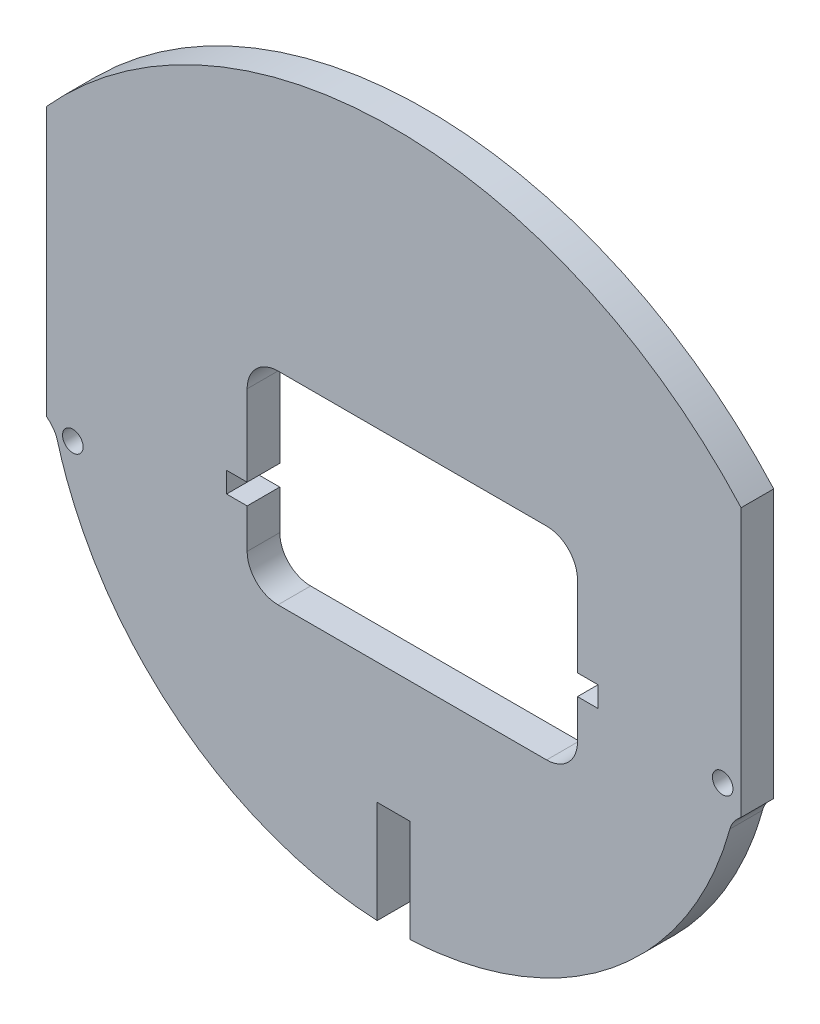
SolidWorks part; units mm, degrees
ref_plane "Front Plane" through (0, 0, 0) normal (0, 0, 1) x (1, 0, 0)
ref_plane "Top Plane" through (0, 0, 0) normal (0, 1, 0) x (1, 0, 0)
ref_plane "Right Plane" through (0, 0, 0) normal (1, 0, 0) x (0, 0, -1)
sketch "Sketch1" plane through (0, 0, 299.79) normal (0, 0, 1) x (1, 0, 0)
  line L4 (33.8, -7.3668) -> (33.8, 18.7258)
  line L5 (-33.8, 18.7232) -> (-33.8, -7.3668)
  line L6 (33.8, -7.3668) -> (33.8, 18.7258)
  line L7 (-33.8, 18.7232) -> (-33.8, -7.3668)
  arc A2 (33.8, 18.7258) -> (-33.8, 18.7232) centre (0.0012, -11.6296) ccw
  arc A3 (33.8, 18.7258) -> (-33.8, 18.7232) centre (0.0012, -11.6296) ccw
  spline S8 degree 3 poles (-1016.2927, 2781.193) (-581.3061, 1300.0591) (-161.7758, -90.3852) (11.2723, -31.8769) (11.7093, -31.7192) (12.5722, -31.3883) (13.8533, -30.8679) (16.7482, -29.4839) (19.0662, -28.003) (20.9048, -26.6015) (21.2687, -26.3121) (21.9818, -25.721) (22.3313, -25.4192) (23.3593, -24.4955) (25.3334, -22.5755) (27.0578, -20.4334) (28.6095, -18.1378) (29.099, -17.3449) (30.0051, -15.7345) (30.4243, -14.9144) (73.6573, 78.615) (-299.6884, 354.0447) (-2573.4248, 1463.866) knots -12.045008 -12.045008 -12.045008 -12.045008 0.25 0.25 0.28125 0.28125 0.3125 0.375 0.5 0.5 0.53125 0.53125 0.5625 0.5625 0.625 0.75 0.75 0.8125 0.8125 0.875 0.875 7.815594 7.815594 7.815594 7.815594 only from (0, -33.7996) to (32.7115, -8.8898)
  spline S9 degree 3 poles (3012.7008, -332.9993) (194.5659, -142.2921) (21.2536, -24.2042) (45.0624, 8.2078) (207.3281, -123.8641) (-2059.6696, 2140.7862) knots -30.844141 -30.844141 -30.844141 -30.844141 0.5 0.5 32.000269 32.000269 32.000269 32.000269 only from (32.7115, -8.8898) to (33.8, -7.3668)
  spline S10 degree 3 poles (1931.9323, 2258.2217) (-186.0941, -116.3959) (-47.7859, 6.5702) (-33.3262, -7.7914) (-33.2211, -7.9122) (-33.0345, -8.1665) (-32.9521, -8.3007) (-26.9906, -20.3777) (-108.782, -90.3547) (-1945.2248, 2299.9192) knots -31.496025 -31.496025 -31.496025 -31.496025 0.25 0.25 0.5 0.5 0.75 0.75 21.739069 21.739069 21.739069 21.739069 only from (-33.8, -7.3668) to (-32.7115, -8.8898)
  spline S11 degree 3 poles (2544.6593, 1514.4209) (266.9927, 341.713) (-71.9551, 75.0102) (-30.0469, -15.7324) (-29.1497, -17.3351) (-27.8537, -19.2568) (-27.5859, -19.6367) (-27.0375, -20.381) (-26.1942, -21.4772) (-25.2894, -22.5133) (-23.4001, -24.5077) (-22.0369, -25.736) (-20.1986, -27.1404) (-19.8234, -27.4151) (-18.307, -28.4773) (-17.131, -29.1958) (-14.2997, -30.6962) (-12.6159, -31.4206) (-9.9927, -32.3105) (-9.0996, -32.5737) (-7.3094, -33.0214) (-6.4087, -33.2074) (264.603, -77.6051) (1022.8864, 3211.8785) (666.5513, -1110.289) knots -6.570571 -6.570571 -6.570571 -6.570571 0.125 0.125 0.25 0.25 0.28125 0.28125 0.3125 0.375 0.375 0.5 0.5 0.53125 0.53125 0.625 0.625 0.75 0.75 0.8125 0.8125 0.875 0.875 19.504434 19.504434 19.504434 19.504434 only from (-32.7115, -8.8898) to (0, -33.7996)
  spline S12 degree 3 poles (0, -33.7996) (3.712, -33.7995) (7.3238, -33.2119) (11.2723, -31.8769) (11.7093, -31.7192) (12.5722, -31.3883) (13.8533, -30.8679) (16.7482, -29.4839) (19.0662, -28.003) (20.9048, -26.6015) (21.2687, -26.3121) (21.9818, -25.721) (22.3313, -25.4192) (23.3593, -24.4955) (25.3334, -22.5755) (27.0578, -20.4334) (28.6095, -18.1378) (29.099, -17.3449) (30.0051, -15.7345) (30.4243, -14.9144) (31.5818, -12.4103) (32.2185, -10.6815) (32.7115, -8.8898) knots 0 0 0 0 0.25 0.25 0.28125 0.28125 0.3125 0.375 0.5 0.5 0.53125 0.53125 0.5625 0.5625 0.625 0.75 0.75 0.8125 0.8125 0.875 0.875 1 1 1 1
  spline S13 degree 3 poles (32.7115, -8.8898) (32.7967, -8.5801) (32.939, -8.2963) (33.3179, -7.7806) (33.5452, -7.5601) (33.8, -7.3668) knots 0 0 0 0 0.5 0.5 1 1 1 1
  spline S14 degree 3 poles (-33.8, -7.3668) (-33.6728, -7.4633) (-33.5521, -7.567) (-33.3262, -7.7914) (-33.2211, -7.9122) (-33.0345, -8.1665) (-32.9521, -8.3007) (-32.8117, -8.585) (-32.754, -8.7354) (-32.7115, -8.8898) knots 0 0 0 0 0.25 0.25 0.5 0.5 0.75 0.75 1 1 1 1
  spline S15 degree 3 poles (-32.7115, -8.8898) (-32.2185, -10.6814) (-31.583, -12.4063) (-30.0469, -15.7324) (-29.1497, -17.3351) (-27.8537, -19.2568) (-27.5859, -19.6367) (-27.0375, -20.381) (-26.1942, -21.4772) (-25.2894, -22.5133) (-23.4001, -24.5077) (-22.0369, -25.736) (-20.1986, -27.1404) (-19.8234, -27.4151) (-18.307, -28.4773) (-17.131, -29.1958) (-14.2997, -30.6962) (-12.6159, -31.4206) (-9.9927, -32.3105) (-9.0996, -32.5737) (-7.3094, -33.0214) (-4.6073, -33.5794) (-1.8558, -33.7996) (0, -33.7996) knots 0 0 0 0 0.125 0.125 0.25 0.25 0.28125 0.28125 0.3125 0.375 0.375 0.5 0.5 0.53125 0.53125 0.625 0.625 0.75 0.75 0.8125 0.8125 0.875 1 1 1 1
  dimension "D1" = 1
extrude "Boss-Extrude1" add sketch "Sketch1" against normal blind 3.175
sketch "Sketch2" plane through (0, 0, 296.615) normal (0, 0, -1) x (-1, 0, 0)
  line L4 (-23.8, 14.6162) -> (-23.8, -4.2553)
  line L5 (23.8, -4.2556) -> (23.8, 14.6141)
  line L6 (-23.8, 14.6162) -> (-23.8, -4.2553)
  line L7 (23.8, -4.2556) -> (23.8, 14.6141)
  arc A2 (23.8, 14.6141) -> (-23.8, 14.6162) centre (-0.0012, -11.6296) ccw
  arc A3 (23.8, 14.6141) -> (-23.8, 14.6162) centre (-0.0012, -11.6296) ccw
  circle A4 centre (-32.0093, -5.359) radius 1
  circle A5 centre (-32.0093, -5.359) radius 1
  circle A6 centre (31.2161, -8.1644) radius 1
  circle A7 centre (31.2161, -8.1644) radius 1
  spline S8 degree 3 poles (2588.6585, 1461.9481) (237.4059, 279.2145) (-53.6805, 59.1859) (-21.188, -11.0621) (-20.5557, -12.1928) (-19.4591, -13.8197) (-19.0712, -14.346) (-18.2586, -15.3576) (-17.8329, -15.8444) (-16.4995, -17.2501) (-15.5379, -18.1162) (-13.9825, -19.3052) (-13.4457, -19.6815) (-12.3523, -20.3817) (-11.7936, -20.7074) (-10.0819, -21.6131) (-8.8941, -22.123) (-7.0446, -22.7511) (-6.4151, -22.9369) (-5.1531, -23.2528) (-4.5182, -23.3839) (146.6784, -48.1096) (514.4313, 1408.8154) (23.9713, -2988.3593) knots -7.237863 -7.237863 -7.237863 -7.237863 0.125 0.125 0.25 0.25 0.3125 0.3125 0.375 0.375 0.5 0.5 0.5625 0.5625 0.625 0.625 0.75 0.75 0.8125 0.8125 0.875 0.875 15.604534 15.604534 15.604534 15.604534 only from (-23.0698, -6.2368) to (0, -23.7996)
  spline S9 degree 3 poles (-2928.51, -741.6682) (-53.0027, 117.8572) (1751.1569, 582.5973) (-2739.2696, -1272.1811) knots -147.93974 -147.93974 -147.93974 -147.93974 118.763391 118.763391 118.763391 118.763391 only from (-23.8, -4.2553) to (-23.0698, -6.2368)
  spline S10 degree 3 poles (2745.3916, -1259.0395) (-4951.2339, 1886.1992) (6692.7962, -2096.1576) (1214.6192, 231.5182) knots -110.892959 -110.892959 -110.892959 -110.892959 300.787119 300.787119 300.787119 300.787119 only from (23.0698, -6.2368) to (23.8, -4.2556)
  spline S11 degree 3 poles (-870.5324, 810.2078) (-1093.2425, 3555.5343) (-224.363, -101.0834) (8.2579, -22.3397) (8.8686, -22.106) (10.0606, -21.5942) (10.6439, -21.3154) (12.3557, -20.4105) (13.4453, -19.7143) (15.0007, -18.5277) (15.506, -18.1092) (16.4726, -17.2408) (16.9364, -16.7892) (18.2706, -15.3838) (19.0816, -14.3772) (20.1754, -12.7583) (20.5206, -12.1991) (21.1595, -11.0633) (21.4548, -10.4848) (54.7957, 61.5445) (-261.3264, 286.2476) (-2618.6825, 1406.8637) knots -23.18789 -23.18789 -23.18789 -23.18789 0.25 0.25 0.3125 0.3125 0.375 0.375 0.5 0.5 0.5625 0.5625 0.625 0.625 0.75 0.75 0.8125 0.8125 0.875 0.875 8.46157 8.46157 8.46157 8.46157 only from (0, -23.7996) to (23.0698, -6.2368)
  spline S12 degree 3 poles (-23.0698, -6.2368) (-22.7221, -7.5005) (-22.2728, -8.7167) (-21.188, -11.0621) (-20.5557, -12.1928) (-19.4591, -13.8197) (-19.0712, -14.346) (-18.2586, -15.3576) (-17.8329, -15.8444) (-16.4995, -17.2501) (-15.5379, -18.1162) (-13.9825, -19.3052) (-13.4457, -19.6815) (-12.3523, -20.3817) (-11.7936, -20.7074) (-10.0819, -21.6131) (-8.8941, -22.123) (-7.0446, -22.7511) (-6.4151, -22.9369) (-5.1531, -23.2528) (-4.5182, -23.3839) (-2.6016, -23.6973) (-1.3083, -23.7996) (0, -23.7996) knots 0 0 0 0 0.125 0.125 0.25 0.25 0.3125 0.3125 0.375 0.375 0.5 0.5 0.5625 0.5625 0.625 0.625 0.75 0.75 0.8125 0.8125 0.875 0.875 1 1 1 1
  spline S13 degree 3 poles (-23.8, -4.2553) (-23.5007, -4.8952) (-23.2572, -5.5557) (-23.0698, -6.2368) knots 0 0 0 0 1 1 1 1
  spline S14 degree 3 poles (23.0698, -6.2368) (23.2572, -5.5558) (23.5008, -4.8954) (23.8, -4.2556) knots 0 0 0 0 1 1 1 1
  spline S15 degree 3 poles (0, -23.7996) (2.6175, -23.7995) (5.1646, -23.3868) (8.2579, -22.3397) (8.8686, -22.106) (10.0606, -21.5942) (10.6439, -21.3154) (12.3557, -20.4105) (13.4453, -19.7143) (15.0007, -18.5277) (15.506, -18.1092) (16.4726, -17.2408) (16.9364, -16.7892) (18.2706, -15.3838) (19.0816, -14.3772) (20.1754, -12.7583) (20.5206, -12.1991) (21.1595, -11.0633) (21.4548, -10.4848) (22.2721, -8.7192) (22.7221, -7.5005) (23.0698, -6.2368) knots 0 0 0 0 0.25 0.25 0.3125 0.3125 0.375 0.375 0.5 0.5 0.5625 0.5625 0.625 0.625 0.75 0.75 0.8125 0.8125 0.875 0.875 1 1 1 1
  dimension "D1" = 10
  dimension "D2" = 0
  dimension "D3" = 0
extrude "Cut-Extrude1" cut sketch "Sketch2" against normal blind 3.175 contours A7 | A5
sketch "Sketch3" plane through (0, 0, 299.79) normal (0, 0, 1) x (1, 0, 0)
  line L0 (-1.6006, -34.7702) -> (1.5744, -34.7702) construction
  line L1 (-1.6006, -23.7996) -> (-1.6006, -34.7702) construction
  line L2 (-1.6006, -23.7996) -> (1.5744, -23.7996) construction
  line L3 (1.5744, -34.7702) -> (1.5744, -23.7996) construction
  line L4 (-1.6006, -34.7702) -> (1.5744, -34.7702)
  line L5 (-1.6006, -23.7996) -> (-1.6006, -34.7702)
  line L6 (-1.6006, -23.7996) -> (1.5744, -23.7996)
  line L7 (1.5744, -34.7702) -> (1.5744, -23.7996)
extrude "Cut-Extrude2" cut sketch "Sketch3" against normal through all
sketch "Sketch4" plane through (0, 0, 296.615) normal (0, 0, -1) x (-1, 0, 0)
  line L4 (11.2577, 7.7172) -> (-14.8786, 7.7172)
  line L5 (11.2577, 7.7172) -> (-14.8786, 7.7172)
  line L6 (-17.8786, 4.7172) -> (-17.8786, -8.9843)
  line L7 (-17.8786, 4.7172) -> (-17.8786, -8.9843)
  line L32 (-14.8786, -11.9843) -> (11.2577, -11.9843)
  line L33 (-14.8786, -11.9843) -> (11.2577, -11.9843)
  line L34 (14.2577, -8.9843) -> (14.2577, 4.7172)
  line L35 (14.2577, -8.9843) -> (14.2577, 4.7172)
  line L108 (-19.8786, -3.1502) -> (-19.8786, -5.1502) construction
  line L109 (-19.8786, -5.1502) -> (-17.8786, -5.1502) construction
  line L110 (-17.8786, -5.1502) -> (-17.8786, -3.1502) construction
  line L111 (-17.8786, -3.1502) -> (-19.8786, -3.1502) construction
  line L115 (14.2577, -3.1502) -> (16.2577, -3.1502) construction
  line L116 (14.2577, -5.1502) -> (14.2577, -3.1502) construction
  line L117 (16.2577, -5.1502) -> (14.2577, -5.1502) construction
  line L123 (-19.8786, -3.1502) -> (-19.8786, -5.1502)
  line L124 (-19.8786, -5.1502) -> (-17.8786, -5.1502)
  line L125 (-17.8786, -5.1502) -> (-17.8786, -3.1502)
  line L126 (-17.8786, -3.1502) -> (-19.8786, -3.1502)
  line L127 (16.2577, -3.1502) -> (16.2577, -5.1502)
  line L130 (14.2577, -3.1502) -> (16.2577, -3.1502)
  line L131 (14.2577, -5.1502) -> (14.2577, -3.1502)
  line L132 (16.2577, -5.1502) -> (14.2577, -5.1502)
  arc A28 (-14.8786, 7.7172) -> (-17.8786, 4.7172) centre (-14.8786, 4.7172) ccw
  arc A29 (-14.8786, 7.7172) -> (-17.8786, 4.7172) centre (-14.8786, 4.7172) ccw
  arc A30 (-17.8786, -8.9843) -> (-14.8786, -11.9843) centre (-14.8786, -8.9843) ccw
  arc A31 (-17.8786, -8.9843) -> (-14.8786, -11.9843) centre (-14.8786, -8.9843) ccw
  arc A32 (11.2577, -11.9843) -> (14.2577, -8.9843) centre (11.2577, -8.9843) ccw
  arc A33 (11.2577, -11.9843) -> (14.2577, -8.9843) centre (11.2577, -8.9843) ccw
  arc A34 (14.2577, 4.7172) -> (11.2577, 7.7172) centre (11.2577, 4.7172) ccw
  arc A35 (14.2577, 4.7172) -> (11.2577, 7.7172) centre (11.2577, 4.7172) ccw
  dimension "D1" = 0
extrude "Cut-Extrude3" cut sketch "Sketch4" against normal through all contours L35 A35 L5 A29 L7 A31 L33 A33 | L132 L127 L130 L35 | L126 L123 L124 L125 region at (1.8104, -2.1335, 296.615) region at (-15.2577, -4.1502, 296.615)
